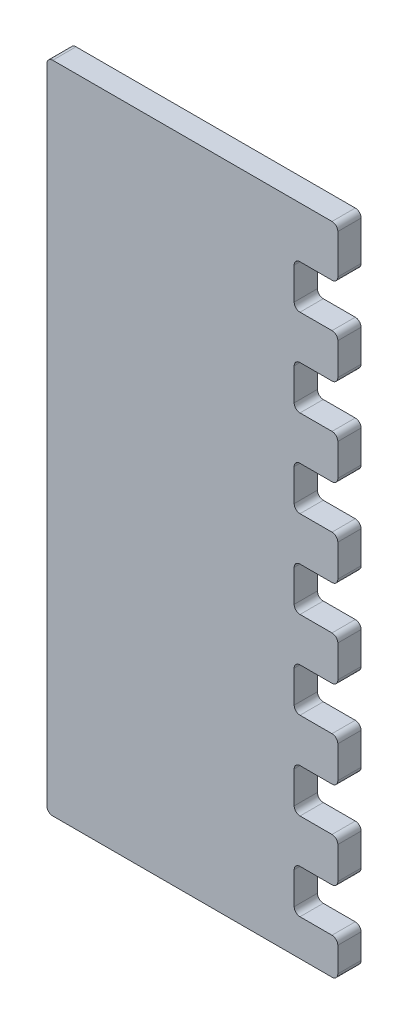
SolidWorks part; units mm, degrees
ref_plane "Front Plane" through (0, 0, 0) normal (0, 0, 1) x (1, 0, 0)
ref_plane "Top Plane" through (0, 0, 0) normal (0, 1, 0) x (1, 0, 0)
ref_plane "Right Plane" through (0, 0, 0) normal (1, 0, 0) x (0, 0, -1)
sketch "Sketch1" plane through (0, 0, 0) normal (0, 0, 1) x (1, 0, 0)
  line L1 (-100, 0) -> (100, 0)
  line L2 (-100, 0) -> (-100, 450)
  line L3 (-100, 450) -> (100, 450)
  line L4 (100, 0) -> (100, 450)
  point P4 (0, 0)
  dimension "D1" = 200
  dimension "D2" = 450
extrude "Boss-Extrude1" add sketch "Sketch1" along normal blind 16
sketch "Sketch2" plane through (0, 0, 16) normal (0, 0, 1) x (1, 0, 0)
  line L0 (100, 0) -> (100, 25)
  line L1 (100, 0) -> (100, 450) construction
  line L2 (100, 25) -> (70, 25)
  line L3 (70, 25) -> (70, 55)
  line L4 (70, 55) -> (100, 55)
  line L5 (70, 110) -> (100, 110)
  line L6 (70, 80) -> (70, 110)
  line L7 (100, 80) -> (70, 80)
  line L8 (100, 55) -> (100, 80)
  line L9 (70, 165) -> (100, 165)
  line L10 (70, 135) -> (70, 165)
  line L11 (100, 135) -> (70, 135)
  line L12 (100, 110) -> (100, 135)
  line L13 (70, 220) -> (100, 220)
  line L14 (70, 190) -> (70, 220)
  line L15 (100, 190) -> (70, 190)
  line L16 (100, 165) -> (100, 190)
  line L17 (70, 275) -> (100, 275)
  line L18 (70, 245) -> (70, 275)
  line L19 (100, 245) -> (70, 245)
  line L20 (100, 220) -> (100, 245)
  line L21 (70, 330) -> (100, 330)
  line L22 (70, 300) -> (70, 330)
  line L23 (100, 300) -> (70, 300)
  line L24 (100, 275) -> (100, 300)
  line L25 (70, 385) -> (100, 385)
  line L26 (70, 355) -> (70, 385)
  line L27 (100, 355) -> (70, 355)
  line L28 (100, 330) -> (100, 355)
  line L29 (70, 440) -> (100, 440)
  line L30 (70, 410) -> (70, 440)
  line L31 (100, 410) -> (70, 410)
  line L32 (100, 385) -> (100, 410)
  line L33 (70, 495) -> (100, 495)
  line L34 (70, 465) -> (70, 495)
  line L35 (100, 465) -> (70, 465)
  line L36 (100, 440) -> (100, 465)
  line L37 (70, 550) -> (100, 550)
  line L38 (70, 520) -> (70, 550)
  line L39 (100, 520) -> (70, 520)
  line L40 (100, 495) -> (100, 520)
  line L41 (70, 605) -> (100, 605)
  line L42 (70, 575) -> (70, 605)
  line L43 (100, 575) -> (70, 575)
  line L44 (100, 550) -> (100, 575)
  line L45 (70, 660) -> (100, 660)
  line L46 (70, 630) -> (70, 660)
  line L47 (100, 630) -> (70, 630)
  line L48 (100, 605) -> (100, 630)
  line L49 (70, 715) -> (100, 715)
  line L50 (70, 685) -> (70, 715)
  line L51 (100, 685) -> (70, 685)
  line L52 (100, 660) -> (100, 685)
  line M3 (100, 0) -> (100, 450)
  dimension "D1" = 25
  dimension "D2" = 30
  dimension "D3" = 30
  dimension "D4" = 13
extrude "Cut-Extrude8" cut sketch "Sketch2" against normal through all both and the other way through all contours L4 L3 L2 M3 region at (85, 40, 16)
pattern_linear "LPattern1" count 7 spacing 60 along (0, 1, 0) of "Cut-Extrude8"
fillet "Fillet1" radius 4 32 edges at (100, 145, 8) (70, 145, 8) (70, 175, 8) (100, 175, 8) (100, 205, 8) (70, 205, 8) (70, 235, 8) (100, 235, 8) (100, 265, 8) (70, 265, 8) (70, 295, 8) (100, 295, 8) (100, 325, 8) (70, 355, 8) (100, 355, 8) (100, 385, 8) (70, 385, 8) (70, 415, 8) (100, 415, 8) (100, 450, 8) (-100, 450, 8) (-100, 0, 8) (100, 0, 8) (100, 25, 8) (70, 25, 8) (70, 55, 8) (100, 55, 8) (100, 85, 8) (70, 85, 8) (70, 115, 8) (100, 115, 8) (70, 325, 8)
